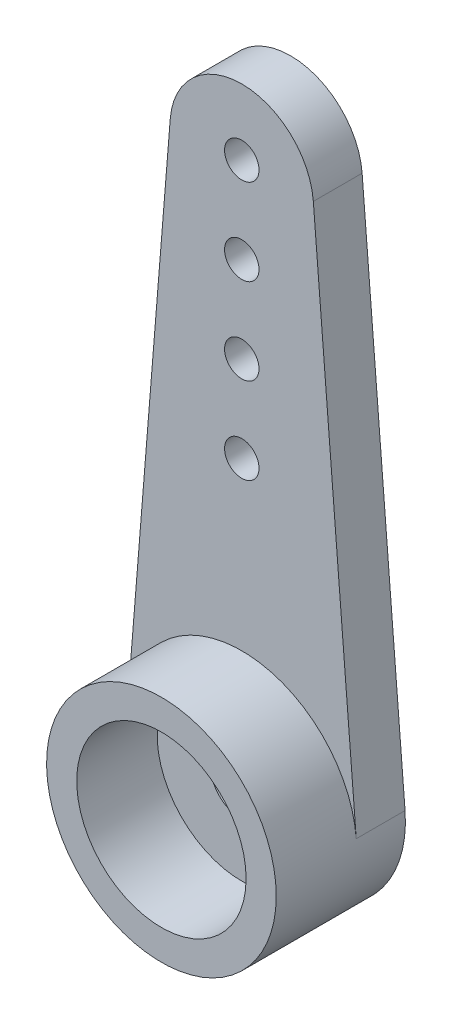
SolidWorks part; units mm, degrees
ref_plane "Спереди" through (0, 0, 0) normal (0, 0, 1) x (1, 0, 0)
ref_plane "Сверху" through (0, 0, 0) normal (0, 1, 0) x (1, 0, 0)
ref_plane "Справа" through (0, 0, 0) normal (1, 0, 0) x (0, 0, -1)
sketch "Эскиз1" plane through (0, 0, 0) normal (0, 0, 1) x (1, 0, 0)
  circle A0 centre (0, 0) radius 4
  circle A1 centre (0, 0) radius 2.5
  circle A2 centre (0, 0) radius 1.1
  circle A3 centre (0, 0) radius 2.95
  dimension "D1" = 8
  dimension "D2" = 5
  dimension "D3" = 2.2
  dimension "D4" = 5.9
extrude "Бобышка-Вытянуть1" add sketch "Эскиз1" along normal blind 4.5 contours A0 A3 region at (-3.8869, 0, 0)
extrude "Бобышка-Вытянуть2" add sketch "Эскиз1<3>" along normal blind 1.7 contours A3 A1 | A1 A2 region at (-2.4293, 0, 0) region at (-2.8666, 0, 0)
sketch "Эскиз1<3>" plane through (0, 0, 0) normal (0, 0, 1) x (1, 0, 0) same geometry as "Эскиз1"
extrude "Вырез-Вытянуть1" cut sketch "Эскиз1<4>" along normal blind 0.4 contours A3 A1 | A1 A2 region at (-2.4293, 0, 0) region at (-2.8666, 0, 0)
sketch "Эскиз1<4>" plane through (0, 0, 0) normal (0, 0, 1) x (1, 0, 0) same geometry as "Эскиз1"
sketch "Эскиз2" plane through (0, 0, 0) normal (0, 0, 1) x (1, 0, 0)
  line L0 (0, 0) -> (0, 27.4115) construction
  line L1 (-2.4919, 18.8016) -> (-3.987, 0.3226)
  line L2 (2.4919, 18.8016) -> (3.987, 0.3226)
  line L3 (-7.4124, 21.1) -> (12.2553, 21.1) construction
  line L4 (-2.4919, 18.8016) -> (2.4919, 18.8016) construction
  circle A0 centre (0, 0) radius 4 construction
  circle A1 centre (0, 0) radius 4
  arc A2 (-2.4919, 18.8016) -> (2.4919, 18.8016) centre (0, 18.6) cw
  circle A3 centre (0, 18.8016) radius 0.6
  circle A4 centre (0, 15.8016) radius 0.6
  circle A5 centre (0, 12.8016) radius 0.6
  circle A6 centre (0, 9.8016) radius 0.6
  point P9 (0, 49.6)
  dimension "D1" = 2.5
  dimension "D3" = 1.2
  dimension "D2" = 17.1
  dimension "D4" = 1.8
  dimension "D5" = 1.8
  dimension "D6" = 1.8
extrude "Бобышка-Вытянуть3" add sketch "Эскиз2" along normal blind 1.7 contours A2 L1 A1 L2 A6 A5 A4 A3 region at (0, 11.1079, 0)
sketch "Sketch1" plane through (0, 0, 0) normal (0, 0, -1) x (-1, 0, 0)
  line L0 (0, 0) -> (0, 21.1) construction
  arc A0 (2.4919, 18.8016) -> (-2.4919, 18.8016) centre (0, 18.6) ccw construction
equation "\"D1@Бобышка-Вытянуть2\"=4.5-2.8"
equation "\"D4@Эскиз2\"=4.2-2.4"
equation "\"D5@Эскиз2\"=\"D4@Эскиз2\""
equation "\"D6@Эскиз2\"=\"D5@Эскиз2\""
